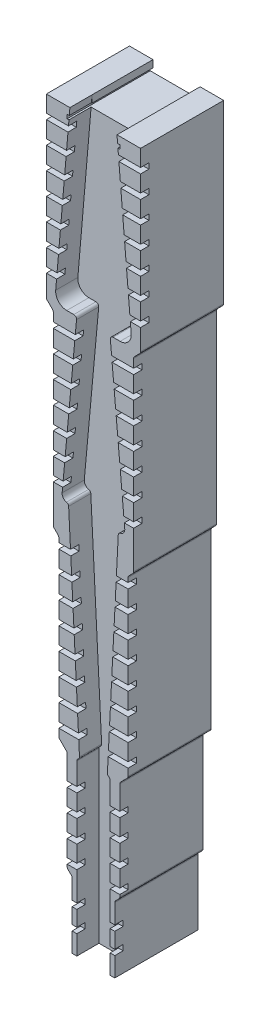
SolidWorks part; units mm, degrees
ref_plane "Plan de face" through (0, 0, 0) normal (0, 0, 1) x (1, 0, 0)
ref_plane "Plan de dessus" through (0, 0, 0) normal (0, 1, 0) x (1, 0, 0)
ref_plane "Plan de droite" through (0, 0, 0) normal (1, 0, 0) x (0, 0, -1)
sketch "Esquisse1" plane through (0, 0, 0) normal (0, 0, 1) x (1, 0, 0)
  line L1 (-8.5, 66) -> (8.5, 66)
  line L2 (-8.5, 66) -> (-8.5, -66)
  line L3 (-8.5, -66) -> (8.5, -66)
  line L4 (8.5, 66) -> (8.5, -66)
  dimension "D1" = 17
  dimension "D2" = 132
  dimension "D3" = 66
  dimension "D4" = 8.5
extrude "Boss.-Extru.1" add sketch "Esquisse1" along normal blind 15
sketch "Esquisse2" plane through (0, 0, 15) normal (0, 0, 1) x (1, 0, 0)
  line L0 (0, -66) -> (0, 66)
  line L1 (-8.5, -66) -> (8.5, -66) construction
  line L2 (8.5, 66) -> (-8.5, 66) construction
  line L3 (4.25, 66) -> (7, 34)
  line L4 (7, 34) -> (3, 34)
  line L5 (3, 34) -> (5.75, 4)
  line L6 (5.75, 4) -> (4.5, 4)
  line L7 (4.5, 4) -> (2.5, -35)
  line L8 (3, -35) -> (3, -66)
  line L9 (3, -66) -> (0, -66)
  line L10 (8.5, -66) -> (8.5, 66) construction
  line L11 (2.5, -35) -> (3, -35)
  line L12 (8.5, 66) -> (4.25, 66)
  line L13 (0, 66) -> (4.25, 66)
  line L16 (-8.5, 66) -> (-8.5, -66)
  line L17 (-8.5, -66) -> (8.5, -66)
  line L18 (8.5, -66) -> (8.5, 66)
  line L19 (8.5, 66) -> (-8.5, 66)
  line L20 (-8.5, 66) -> (-8.5, -66)
  line L21 (-8.5, -66) -> (8.5, -66)
  line L22 (8.5, -66) -> (8.5, 66)
  line L23 (0, 66) -> (-8.5, 66)
  dimension "D10" = 31
  dimension "D1" = 4.25
  dimension "D2" = 1.5
  dimension "D3" = 5.5
  dimension "D4" = 2.75
  dimension "D5" = 4
  dimension "D6" = 6
  dimension "D7" = 5.5
  dimension "D8" = 5.5
  dimension "D9" = 31
  dimension "D11" = 70
  dimension "D12" = 32
  dimension "D13" = 0
extrude "Enlèv. mat.-Extru.1" cut sketch "Esquisse2" against normal blind 4 contours L8 L11 L7 L6 L5 L4 L3 L13 L0 L9
fillet "Congé1" radius 2 1 edges at (7, 34, 13)
fillet "Congé2" radius 0.5 1 edges at (3, 34, 13)
fillet "Congé3" radius 1 1 edges at (5.75, 4, 13)
fillet "Congé4" radius 0.5 1 edges at (4.5, 4, 13)
fillet "Congé6" radius 0.5 1 edges at (3, -35, 13)
fillet "Congé7" radius 0.5 1 edges at (2.5, -35, 13)
sketch "Esquisse4" plane through (0, 0, 15) normal (0, 0, 1) x (1, 0, 0)
  line L0 (8.5, 34) -> (7.25, 32.75)
  line L1 (8.5, -66) -> (8.5, 66) construction
  line L2 (7.25, 32.75) -> (7.25, -1)
  line L3 (7.25, -1) -> (6.25, -2)
  line L4 (6.25, -2) -> (6.25, -33.5)
  line L5 (6.25, -33.5) -> (4.75, -35)
  line L6 (4.75, -35) -> (4.75, -53.1)
  line L7 (4.75, -53.1) -> (3.85, -54)
  line L8 (3.85, -54) -> (3.85, -66)
  line L9 (3, -66) -> (8.5, -66) construction
  line L10 (3.85, -66) -> (8.5, -66)
  line L11 (8.5, -66) -> (8.5, 34)
  line L12 (8.5, 66) -> (4.25, 66) construction
  point P4 (6.375, 66)
  dimension "D1" = 32
  dimension "D2" = 135
  dimension "D3" = 1.25
  dimension "D4" = 68
  dimension "D5" = 12
  dimension "D6" = 4.65
  dimension "D7" = 3.75
  dimension "D8" = 31
  dimension "D9" = 2.25
extrude "Enlèv. mat.-Extru.2" cut sketch "Esquisse4" against normal up to next
fillet "Congé8" radius 0.5 7 edges at (7.25, 32.75, 7.5) (7.25, -1, 7.5) (6.25, -2, 7.5) (6.25, -33.5, 7.5) (4.75, -35, 7.5) (4.75, -53.1, 7.5) (3.85, -54, 7.5)
mirror "Symétrie2" about plane through (0, 0, 0) normal (1, 0, 0) of "Enlèv. mat.-Extru.1", "Congé1", "Congé2", "Congé3", "Congé4", "Congé6", "Congé7", "Enlèv. mat.-Extru.2", "Congé8"
fillet "Congé9" radius 0.5 2 edges at (-8.5, 34, 7.5) (8.5, 34, 7.5)
sketch "Esquisse5" plane through (0, 0, 15) normal (0, 0, 1) x (1, 0, 0)
  line L0 (3, -35.5) -> (3, -66) construction
  line L1 (3, -62.5) -> (3.85, -62.5)
  line L2 (3, -62.5) -> (3, -61.5)
  line L3 (3, -61.5) -> (3.85, -61.5)
  line L4 (3.85, -62.5) -> (3.85, -61.5)
  line L5 (3.85, -54.2071) -> (3.85, -66) construction
  line L6 (3, -66) -> (3.85, -66) construction
  line L7 (3, -57.7) -> (3.85, -57.7)
  line L8 (3, -57.7) -> (3, -58.7)
  line L9 (3, -58.7) -> (3.85, -58.7)
  line L10 (3.85, -57.7) -> (3.85, -58.7)
  line L11 (4.75, -35.2071) -> (4.75, -52.8929) construction
  line L12 (3, -52.5) -> (4.75, -52.5)
  line L13 (3, -52.5) -> (3, -51.5)
  line L14 (3, -51.5) -> (4.75, -51.5)
  line L15 (4.75, -52.5) -> (4.75, -51.5)
  line L16 (3, -35.5) -> (3, -66) construction
  line L17 (3, -48.5) -> (4.75, -48.5)
  line L18 (3, -48.5) -> (3, -47.5)
  line L19 (3, -47.5) -> (4.75, -47.5)
  line L20 (4.75, -48.5) -> (4.75, -47.5)
  line L21 (3, -44.5) -> (4.75, -44.5)
  line L22 (3, -44.5) -> (3, -43.5)
  line L23 (3, -43.5) -> (4.75, -43.5)
  line L24 (4.75, -44.5) -> (4.75, -43.5)
  line L25 (3, -40.5) -> (4.75, -40.5)
  line L26 (3, -40.5) -> (3, -39.5)
  line L27 (3, -39.5) -> (4.75, -39.5)
  line L28 (4.75, -40.5) -> (4.75, -39.5)
  line L29 (3, -66) -> (-3, -66) construction
  line L30 (4.4775, 3.5607) -> (2.5195, -34.6195) construction
  line L31 (2.6538, -32) -> (6.25, -32)
  line L32 (2.6538, -32) -> (2.6538, -31)
  line L33 (2.6538, -31) -> (6.25, -31)
  line L34 (6.25, -32) -> (6.25, -31)
  line L35 (6.25, -2.2071) -> (6.25, -33.2929) construction
  line L36 (4.4775, 3.5607) -> (2.5195, -34.6195) construction
  line L37 (2.859, -28) -> (6.25, -28)
  line L38 (2.859, -28) -> (2.859, -27)
  line L39 (2.859, -27) -> (6.25, -27)
  line L40 (6.25, -28) -> (6.25, -27)
  line L41 (8.5, 34.2071) -> (8.5, 66) construction
  line L42 (3.0641, -24) -> (6.25, -24)
  line L43 (3.0641, -24) -> (3.0641, -23)
  line L44 (3.0641, -23) -> (6.25, -23)
  line L45 (6.25, -24) -> (6.25, -23)
  line L46 (3.2692, -20) -> (6.25, -20)
  line L47 (3.2692, -20) -> (3.2692, -19)
  line L48 (3.2692, -19) -> (6.25, -19)
  line L49 (6.25, -20) -> (6.25, -19)
  line L50 (3.4744, -16) -> (6.25, -16)
  line L51 (3.4744, -16) -> (3.4744, -15)
  line L52 (3.4744, -15) -> (6.25, -15)
  line L53 (6.25, -16) -> (6.25, -15)
  line L54 (6.25, -11) -> (3.6795, -11)
  line L55 (6.25, -11) -> (6.25, -12)
  line L56 (6.25, -12) -> (3.6795, -12)
  line L57 (3.6795, -11) -> (3.6795, -12)
  line L58 (6.25, -7) -> (3.8846, -7)
  line L59 (6.25, -7) -> (6.25, -8)
  line L60 (6.25, -8) -> (3.8846, -8)
  line L61 (3.8846, -7) -> (3.8846, -8)
  line L62 (6.25, -3) -> (4.0897, -3)
  line L63 (6.25, -3) -> (6.25, -4)
  line L64 (6.25, -4) -> (4.0897, -4)
  line L65 (4.0897, -3) -> (4.0897, -4)
  line L66 (8.5, 62) -> (4.5078, 62)
  line L67 (8.5, 62) -> (8.5, 63)
  line L68 (8.5, 63) -> (4.5078, 63)
  line L69 (4.5078, 62) -> (4.5078, 63)
  line L70 (4.25, 66) -> (6.8134, 36.1712) construction
  line L71 (4.25, 66) -> (6.8134, 36.1712) construction
  line L72 (4.8516, 59) -> (8.5, 59)
  line L73 (4.8516, 59) -> (4.8516, 58)
  line L74 (4.8516, 58) -> (8.5, 58)
  line L75 (8.5, 59) -> (8.5, 58)
  line L76 (5.1953, 55) -> (8.5, 55)
  line L77 (5.1953, 55) -> (5.1953, 54)
  line L78 (5.1953, 54) -> (8.5, 54)
  line L79 (8.5, 55) -> (8.5, 54)
  line L80 (8.5, 66) -> (4.25, 66) construction
  line L81 (5.5391, 51) -> (8.5, 51)
  line L82 (5.5391, 51) -> (5.5391, 50)
  line L83 (5.5391, 50) -> (8.5, 50)
  line L84 (8.5, 51) -> (8.5, 50)
  line L85 (5.8828, 47) -> (8.5, 47)
  line L86 (5.8828, 47) -> (5.8828, 46)
  line L87 (5.8828, 46) -> (8.5, 46)
  line L88 (8.5, 47) -> (8.5, 46)
  line L89 (6.2266, 43) -> (8.5, 43)
  line L90 (6.2266, 43) -> (6.2266, 42)
  line L91 (6.2266, 42) -> (8.5, 42)
  line L92 (8.5, 43) -> (8.5, 42)
  line L93 (6.5703, 39) -> (8.5, 39)
  line L94 (6.5703, 39) -> (6.5703, 38)
  line L95 (6.5703, 38) -> (8.5, 38)
  line L96 (8.5, 39) -> (8.5, 38)
  line L97 (3.05, 33.4544) -> (5.65, 5.0913) construction
  line L98 (3.275, 31) -> (7.25, 31)
  line L99 (3.275, 31) -> (3.275, 30)
  line L100 (3.275, 30) -> (7.25, 30)
  line L101 (7.25, 31) -> (7.25, 30)
  line L102 (7.25, 32.5429) -> (7.25, -0.7929) construction
  line L103 (3.05, 33.4544) -> (5.65, 5.0913) construction
  line L104 (3.6417, 27) -> (7.25, 27)
  line L105 (3.6417, 27) -> (3.6417, 26)
  line L106 (3.6417, 26) -> (7.25, 26)
  line L107 (7.25, 27) -> (7.25, 26)
  line L108 (4.0083, 23) -> (7.25, 23)
  line L109 (4.0083, 23) -> (4.0083, 22)
  line L110 (4.0083, 22) -> (7.25, 22)
  line L111 (7.25, 23) -> (7.25, 22)
  line L112 (4.375, 19) -> (7.25, 19)
  line L113 (4.375, 19) -> (4.375, 18)
  line L114 (4.375, 18) -> (7.25, 18)
  line L115 (7.25, 19) -> (7.25, 18)
  line L116 (4.7417, 15) -> (7.25, 15)
  line L117 (4.7417, 15) -> (4.7417, 14)
  line L118 (4.7417, 14) -> (7.25, 14)
  line L119 (7.25, 15) -> (7.25, 14)
  line L120 (5.1083, 11) -> (7.25, 11)
  line L121 (5.1083, 11) -> (5.1083, 10)
  line L122 (5.1083, 10) -> (7.25, 10)
  line L123 (7.25, 11) -> (7.25, 10)
  line L124 (5.475, 7) -> (7.25, 7)
  line L125 (5.475, 7) -> (5.475, 6)
  line L126 (5.475, 6) -> (7.25, 6)
  line L127 (7.25, 7) -> (7.25, 6)
  point P12 (3.425, -66)
  dimension "D1" = 3.5
  dimension "D2" = 4.5
  dimension "D3" = 7.3
  dimension "D4" = 8.3
  dimension "D5" = 13.5
  dimension "D6" = 1
  dimension "D7" = 3
  dimension "D8" = 1
  dimension "D9" = 3
  dimension "D10" = 1
  dimension "D11" = 3
  dimension "D12" = 1
  dimension "D13" = 34
  dimension "D14" = 1
  dimension "D15" = 3
  dimension "D16" = 1
  dimension "D17" = 3
  dimension "D18" = 1
  dimension "D19" = 3
  dimension "D20" = 1
  dimension "D21" = 3
  dimension "D22" = 1
  dimension "D23" = 3
  dimension "D24" = 1
  dimension "D25" = 3
  dimension "D26" = 1
  dimension "D27" = 3
  dimension "D28" = 1
  dimension "D29" = 28
  dimension "D30" = 1
  dimension "D31" = 3
  dimension "D32" = 1
  dimension "D33" = 3
  dimension "D34" = 1
  dimension "D35" = 3
  dimension "D36" = 1
  dimension "D37" = 3
  dimension "D38" = 1
  dimension "D39" = 3
  dimension "D40" = 1
  dimension "D41" = 3
  dimension "D42" = 1
  dimension "D43" = 60
  dimension "D44" = 1
  dimension "D45" = 3
  dimension "D46" = 1
  dimension "D47" = 3
  dimension "D48" = 1
  dimension "D49" = 3
  dimension "D50" = 1
  dimension "D51" = 3
  dimension "D52" = 1
  dimension "D53" = 3
  dimension "D54" = 1
  dimension "D55" = 4
  dimension "D56" = 1
extrude "Enlèv. mat.-Extru.3" cut sketch "Esquisse5" against normal blind 1.5
mirror "Symétrie3" about plane through (0, 0, 0) normal (1, 0, 0) of "Enlèv. mat.-Extru.3"
sketch "Esquisse6" plane through (0, 0, 0) normal (0, 0, -1) x (-1, 0, 0)
  line L0 (-4.25, 66) -> (-4.25, 64.7)
  line L1 (-8.5, 66) -> (8.5, 66) construction
  line L2 (-4.25, 64.7) -> (-4.75, 64.7)
  line L3 (-4.75, 64.7) -> (-4.75, 64)
  line L4 (-4.75, 64) -> (4.75, 64)
  line L5 (4.75, 64) -> (4.75, 64.7)
  line L6 (4.75, 64.7) -> (4.25, 64.7)
  line L7 (4.25, 64.7) -> (4.25, 66)
  line L8 (4.25, 66) -> (-4.25, 66)
  line L9 (8.5, 66) -> (8.5, 34.2071) construction
  dimension "D1" = 9.5
  dimension "D2" = 3.75
  dimension "D3" = 2
  dimension "D4" = 1.3
  dimension "D5" = 1.3
  dimension "D6" = 8.5
  dimension "D7" = 0.5
extrude "Enlèv. mat.-Extru.4" cut sketch "Esquisse6" against normal through all
